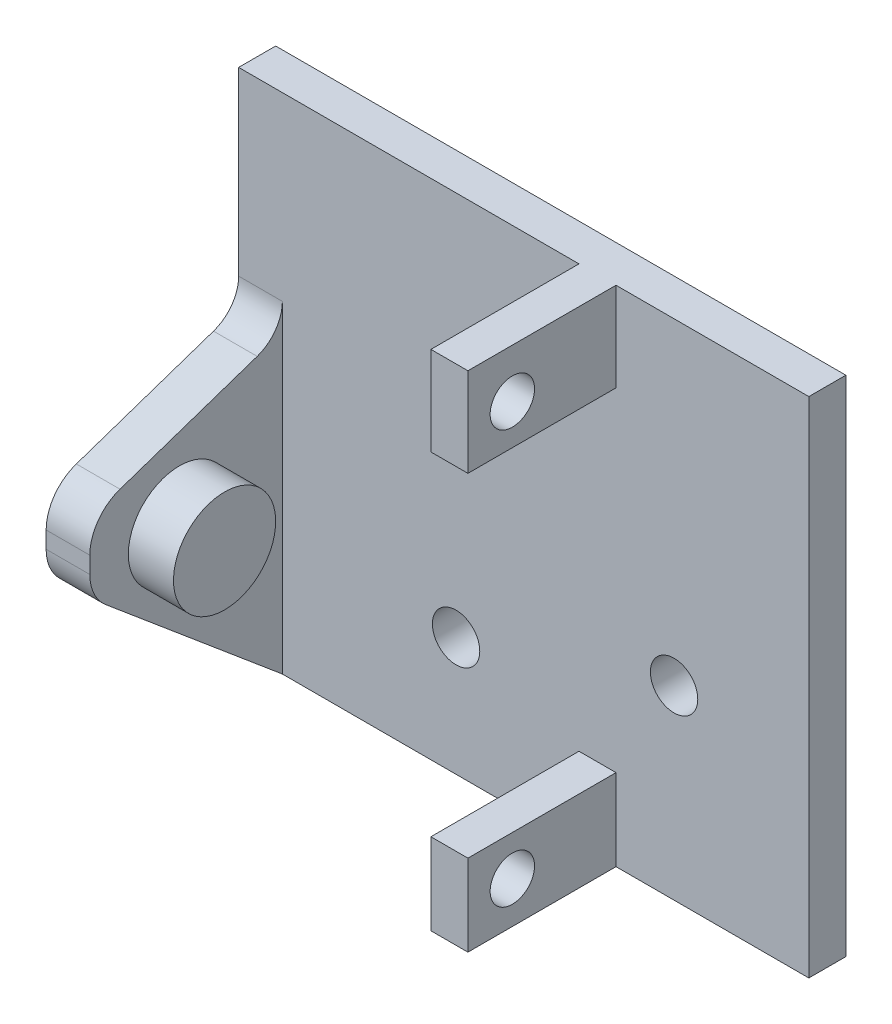
SolidWorks part; units mm, degrees
ref_plane "Plano frontal" through (0, 0, 0) normal (0, 0, 1) x (1, 0, 0)
ref_plane "Plano superior" through (0, 0, 0) normal (0, 1, 0) x (1, 0, 0)
ref_plane "Plano direito" through (0, 0, 0) normal (1, 0, 0) x (0, 0, -1)
sketch "Esboço1" plane through (0, 0, 0) normal (0, 0, 1) x (1, 0, 0)
  line L1 (-22.645, 6.7101) -> (15.855, 6.7101)
  line L2 (-22.645, 6.7101) -> (-22.645, -27.2899)
  line L3 (-22.645, -27.2899) -> (15.855, -27.2899)
  line L4 (15.855, 6.7101) -> (15.855, -27.2899)
  dimension "D1" = 38.5
  dimension "D2" = 34
extrude "Ressalto-extrusão1" add sketch "Esboço1" along normal blind 2.5
sketch "Esboço2" plane through (0, 0, 2.5) normal (0, 0, 1) x (1, 0, 0)
  line L0 (1.585, 6.7101) -> (1.585, -27.2899) construction
  line L1 (15.855, 6.7101) -> (-22.645, 6.7101) construction
  line L3 (0.335, 6.7101) -> (0.335, 0.7101)
  line L4 (0.335, 0.7101) -> (2.835, 0.7101)
  line L5 (2.835, 6.7101) -> (2.835, 0.7101)
  line L6 (0.335, 6.7101) -> (2.835, 6.7101)
  line L7 (-22.645, -21.7899) -> (15.855, -21.7899) construction
  line L8 (-22.645, 6.7101) -> (-22.645, -27.2899) construction
  line L9 (15.855, -27.2899) -> (15.855, 6.7101) construction
  line L28 (0.335, 6.7101) -> (0.335, -27.2899) construction
  line L29 (-22.645, -27.2899) -> (15.855, -27.2899) construction
  line L30 (2.835, 6.7101) -> (2.835, -27.2899) construction
  line L31 (0.335, -27.2899) -> (0.335, -21.7899)
  line L32 (0.335, -21.7899) -> (2.835, -21.7899)
  line L33 (2.835, -21.7899) -> (2.835, -27.2899)
  line L34 (2.835, -27.2899) -> (0.335, -27.2899)
  point P11 (1.585, 0.7101)
  dimension "D1" = 1.25
  dimension "D2" = 22.5
  dimension "D3" = 6
  dimension "D4" = 24.23
  dimension "D5" = 14.27
extrude "Ressalto-extrusão2" add sketch "Esboço2" along normal blind 10
sketch "Esboço3" plane through (2.835, 0, 0) normal (1, 0, 0) x (0, 0, -1)
  line L0 (-9.5, 6.7101) -> (-9.5, 0.7101) construction
  line L1 (-12.5, 6.7101) -> (-2.5, 6.7101) construction
  line L2 (-12.5, 0.7101) -> (-2.5, 0.7101) construction
  line L3 (-2.5, 0.7101) -> (-2.5, 6.7101) construction
  line L4 (-9.5, 6.7101) -> (-9.5, -27.2899) construction
  line L7 (-12.5, -21.7899) -> (-2.5, -21.7899) construction
  circle A0 centre (-9.5, 3.4101) radius 1.5
  circle A1 centre (-9.5, -24.4899) radius 1.5
  point P10 (-9.5, 1.9101)
  point P16 (-9.5, -25.9899)
  point P17 (-9.5, -22.9899)
  dimension "D2" = 1.2
  dimension "D3" = 1.2
  dimension "D1" = 7
extrude "Corte-extrusão1" cut sketch "Esboço3" against normal up to next
sketch "Esboço4" plane through (0, 0, 2.5) normal (0, 0, 1) x (1, 0, 0)
  line L0 (-19.695, 6.7101) -> (-19.695, -27.2899) construction
  line L1 (0.335, 6.7101) -> (-22.645, 6.7101) construction
  line L2 (-22.645, -27.2899) -> (0.335, -27.2899) construction
  line L3 (-22.645, 6.7101) -> (-22.645, -27.2899) construction
  line L4 (-19.695, -27.2899) -> (-19.695, -7.2899)
  line L5 (-19.695, -7.2899) -> (-22.645, -7.2899)
  line L6 (-22.645, -7.2899) -> (-22.645, -27.2899)
  line L7 (-22.645, -27.2899) -> (-19.695, -27.2899)
  point P6 (-19.695, -7.2899)
  dimension "D1" = 2.95
  dimension "D2" = 20
extrude "Ressalto-extrusão3" add sketch "Esboço4" along normal blind 13
sketch "Esboço5" plane through (-22.645, 0, 0) normal (-1, 0, 0) x (0, 0, 1)
  line L0 (2.5, -7.2899) -> (2.5, -27.2899) construction
  line L1 (2.5, -15.0899) -> (15.5, -15.0899) construction
  line L2 (15.5, -7.2899) -> (15.5, -27.2899) construction
  line L3 (15.5, -27.2899) -> (0, -27.2899) construction
  line L4 (2.5, -27.2899) -> (15.5, -16.3664)
  line L6 (15.5, -11.6895) -> (2.5, -7.2899)
  line L7 (15.222, -11.5954) -> (15.222, -16.5999)
  circle A0 centre (9.45, -15.0899) radius 3.45
  line M3 (0, -27.2899) -> (15.5, -27.2899)
  line M4 (15.5, -27.2899) -> (15.5, -7.2899)
  line M5 (15.5, -7.2899) -> (2.5, -7.2899)
  dimension "D2" = 6.95
  dimension "D1" = 12.2
extrude "Corte-extrusão2" cut sketch "Esboço5" against normal blind 15 contours L6 M4 M5 | L4 M3 M4 | A0 region at (-22.645, -23.6487, 11.1667) region at (-22.645, -8.7564, 11.1667) region at (-22.645, -15.0899, 9.45)
fillet "Filete1" radius 3 2 edges at (-21.17, -16.3664, 15.5) (-21.17, -11.6895, 15.5)
fillet "Filete2" radius 2.5 1 edges at (-21.17, -7.2899, 2.5)
sketch "Esboço6" plane through (-19.695, 0, 0) normal (1, 0, 0) x (0, 0, -1)
  circle A0 centre (-9.45, -15.0899) radius 3.45
sketch "Esboço7" plane through (-22.645, 0, 0) normal (-1, 0, 0) x (0, 0, 1)
  circle A0 centre (9.45, -15.0899) radius 3.45
extrude "Ressalto-extrusão5" add sketch "Esboço7" against normal blind 6
sketch "Esboço8" plane through (0, 0, 0) normal (0, 0, -1) x (-1, 0, 0)
  line L0 (7.965, 6.7101) -> (7.965, -27.2899) construction
  line L1 (-15.855, 6.7101) -> (22.645, 6.7101) construction
  line L2 (22.645, -27.2899) -> (-15.855, -27.2899) construction
  line L3 (22.645, 6.7101) -> (22.645, -27.2899) construction
  line L4 (7.965, -19.2899) -> (22.645, -19.2899) construction
  line L6 (-6.755, 6.7101) -> (-6.755, -27.2899) construction
  line L7 (-15.855, -27.2899) -> (-15.855, 6.7101) construction
  line L8 (-15.855, -14.7399) -> (-6.755, -14.7399) construction
  circle A1 centre (7.965, -19.2899) radius 1.6
  circle A2 centre (-6.755, -14.7399) radius 1.6
  dimension "D3" = 3.2
  dimension "D4" = 9.1
  dimension "D6" = 3.2
  dimension "D1" = 14.68
  dimension "D2" = 8
  dimension "D5" = 12.55
extrude "Corte-extrusão3" cut sketch "Esboço8" against normal blind 6
